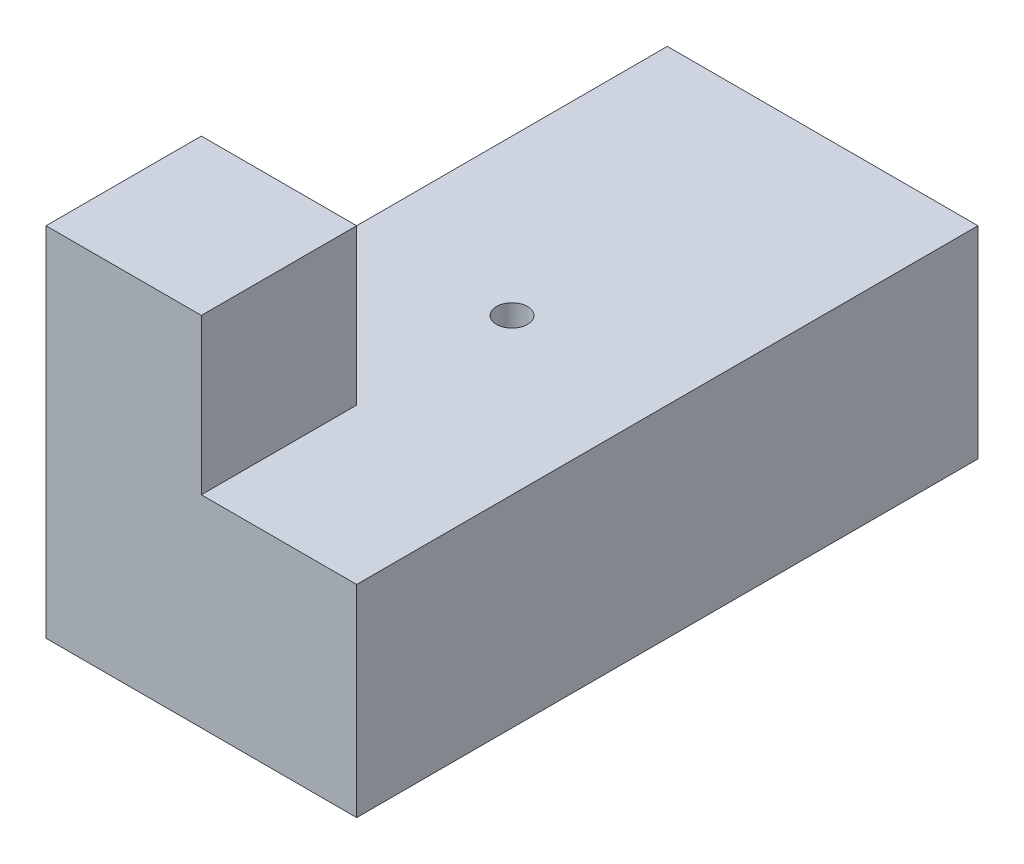
SolidWorks part; units mm, degrees
material "1.7244 (18CrMoS4)"
ref_plane "Front Plane" through (0, 0, 0) normal (0, 0, 1) x (1, 0, 0)
ref_plane "Top Plane" through (0, 0, 0) normal (0, 1, 0) x (1, 0, 0)
ref_plane "Right Plane" through (0, 0, 0) normal (1, 0, 0) x (0, 0, -1)
sketch "Sketch1" plane through (0, 0, 0) normal (0, 1, 0) x (1, 0, 0)
  line L1 (0, 200) -> (100, 200)
  line L2 (0, 200) -> (0, 0)
  line L3 (0, 0) -> (100, 0)
  line L4 (100, 200) -> (100, 0)
  dimension "D1" = 100
  dimension "D2" = 200
extrude "Boss-Extrude1" add sketch "Sketch1" along normal blind 65 contours L4 L1 L2 L3 region at (50, 0, -100)
hole_wizard "Ø10.0mm Dowel Hole1" positions "Sketch2" profile "Sketch4" hole size "Ø10.0" standard "ANSI Metric"
sketch "Sketch2" plane through (0, 65, 0) normal (0, 1, 0) x (1, 0, 0)
  line L0 (0, 0) -> (100, 0) construction
  line L1 (0, 200) -> (0, 0) construction
  point P0 (50, 100)
  dimension "D1" = 100
  dimension "D2" = 50
sketch "Sketch4" plane through (50, 65, -100) normal (1, 0, 0) x (0, 0, 1)
  line L0 (0, 0) -> (0, 43.0043)
  line L1 (0, 43.0043) -> (5, 40)
  line L2 (5, 40) -> (5, 0)
  line L5 (5, 0) -> (0, 0)
  line L10 (0, 43.0043) -> (-5, 40) construction
  line L11 (0, -6.35) -> (0, 107.95) construction
  dimension "Hole Dia." = 10
  dimension "Hole Depth" = 40
  dimension "Drill Angle" = 118
sketch "Sketch5" plane through (0, 65, 0) normal (0, 1, 0) x (1, 0, 0)
  line L0 (0, 0) -> (100, 0) construction
  line L1 (0, 0) -> (50, 0)
  line L2 (0, 0) -> (0, 50)
  line L3 (0, 50) -> (50, 50)
  line L4 (50, 0) -> (50, 50)
  line L5 (0, 200) -> (0, 0) construction
  dimension "D1" = 50
  dimension "D2" = 50
extrude "Boss-Extrude2" add sketch "Sketch5" along normal blind 50
